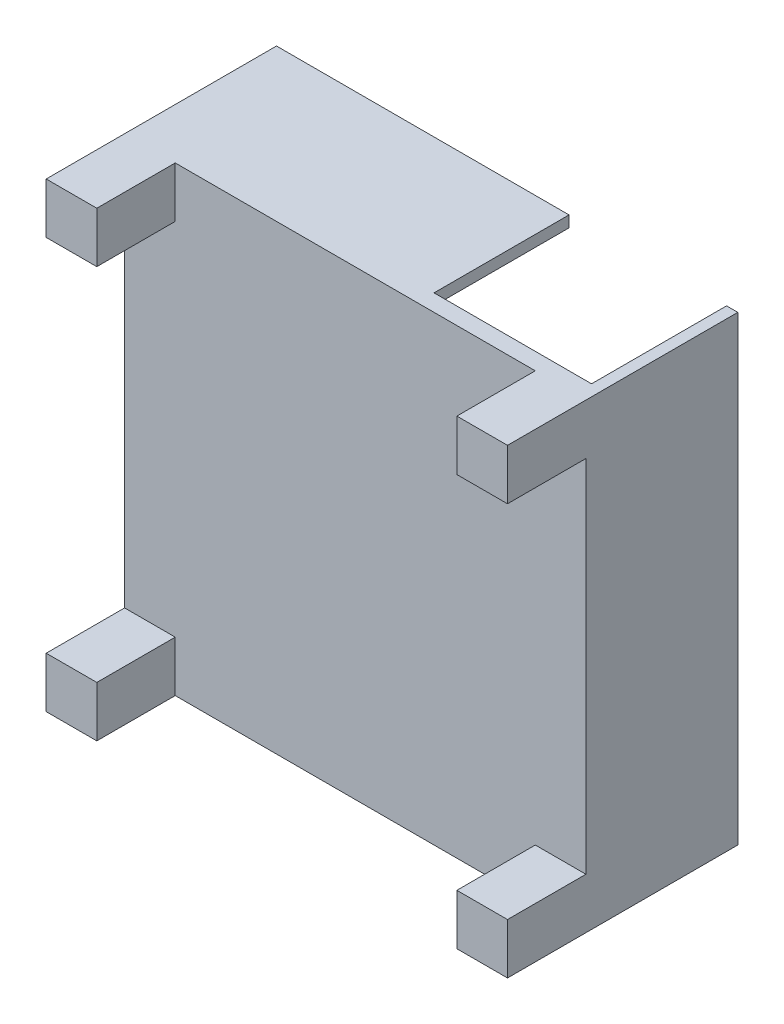
SolidWorks part; units mm, degrees
ref_plane "Piano frontale" through (0, 0, 0) normal (0, 0, 1) x (1, 0, 0)
ref_plane "Piano superiore" through (0, 0, 0) normal (0, 1, 0) x (1, 0, 0)
ref_plane "Piano destro" through (0, 0, 0) normal (1, 0, 0) x (0, 0, -1)
sketch "Schizzo1" plane through (0, 0, 0) normal (0, 0, 1) x (1, 0, 0)
  line L1 (0, 0) -> (41, 0)
  line L2 (0, 0) -> (0, 41)
  line L3 (0, 41) -> (41, 41)
  line L4 (41, 0) -> (41, 41)
  dimension "D1" = 41
  dimension "D2" = 41
extrude "Estrusione-Estrusione1" add sketch "Schizzo1" along normal blind 1.5 contours L1 L4 L3 L2
sketch "Schizzo5" plane through (0, 0, 1.5) normal (0, 0, 1) x (1, 0, 0)
  line L1 (0, 0) -> (4.5, 0)
  line L2 (0, 0) -> (0, 4.5)
  line L3 (0, 4.5) -> (4.5, 4.5)
  line L4 (4.5, 0) -> (4.5, 4.5)
  dimension "D1" = 4.5
  dimension "D2" = 4.5
extrude "Estrusione-Estrusione2" add sketch "Schizzo5" along normal blind 6.97
sketch "Schizzo6" plane through (0, 0, 1.5) normal (0, 0, 1) x (1, 0, 0)
  line L1 (41, 0) -> (36.5, 0)
  line L2 (41, 0) -> (41, 4.5)
  line L3 (41, 4.5) -> (36.5, 4.5)
  line L4 (36.5, 0) -> (36.5, 4.5)
  dimension "D1" = 4.5
  dimension "D2" = 4.5
extrude "Estrusione-Estrusione3" add sketch "Schizzo6" along normal blind 6.97
sketch "Schizzo7" plane through (0, 0, 1.5) normal (0, 0, 1) x (1, 0, 0)
  line L1 (0, 41) -> (4.5, 41)
  line L2 (0, 41) -> (0, 36.5)
  line L3 (0, 36.5) -> (4.5, 36.5)
  line L4 (4.5, 41) -> (4.5, 36.5)
  dimension "D1" = 4.5
  dimension "D2" = 4.5
extrude "Estrusione-Estrusione4" add sketch "Schizzo7" along normal blind 6.97
sketch "Schizzo8" plane through (0, 0, 1.5) normal (0, 0, 1) x (1, 0, 0)
  line L1 (41, 41) -> (36.5, 41)
  line L2 (41, 41) -> (41, 36.5)
  line L3 (41, 36.5) -> (36.5, 36.5)
  line L4 (36.5, 41) -> (36.5, 36.5)
  dimension "D1" = 4.5
  dimension "D2" = 4.5
extrude "Estrusione-Estrusione5" add sketch "Schizzo8" along normal blind 6.97
sketch "Schizzo9" plane through (0, 0, 0) normal (0, 0, -1) x (-1, 0, 0)
  line L0 (0, 0) -> (-41, 0) construction
  line L1 (-41, 41) -> (-40, 41)
  line L2 (-41, 41) -> (-41, 0)
  line L3 (-41, 0) -> (-40, 0)
  line L4 (-40, 41) -> (-40, 0)
  dimension "D1" = 1
  dimension "D2" = 41
extrude "Estrusione-Estrusione6" add sketch "Schizzo9" along normal blind 12
sketch "Schizzo10" plane through (0, 0, 0) normal (0, 0, -1) x (-1, 0, 0)
  line L0 (0, 41) -> (-40, 41) construction
  line L1 (-26, 41) -> (0, 41)
  line L2 (-26, 41) -> (-26, 40)
  line L3 (-26, 40) -> (0, 40)
  line L4 (0, 41) -> (0, 40)
  line L5 (0, 0) -> (0, 41) construction
  dimension "D1" = 26
  dimension "D2" = 1
extrude "Estrusione-Estrusione7" add sketch "Schizzo10" along normal blind 12
